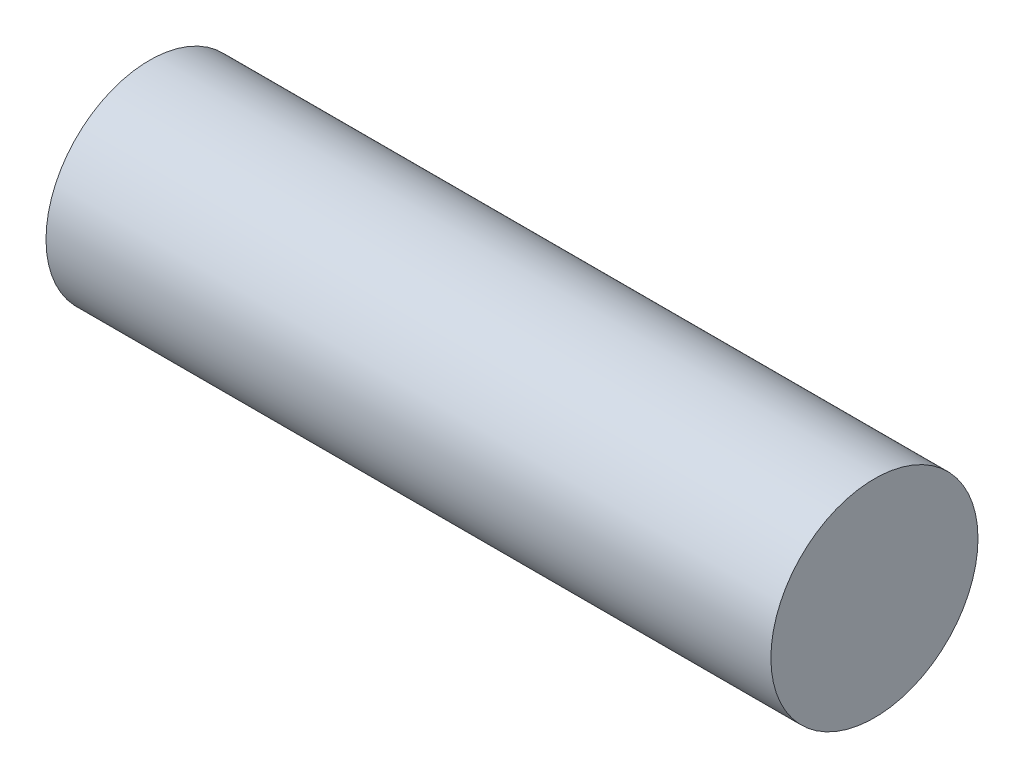
SolidWorks part; units mm, degrees
ref_plane "Front Plane" through (0, 0, 0) normal (0, 0, 1) x (1, 0, 0)
ref_plane "Top Plane" through (0, 0, 0) normal (0, 1, 0) x (1, 0, 0)
ref_plane "Right Plane" through (0, 0, 0) normal (1, 0, 0) x (0, 0, -1)
sketch "Sketch1" plane through (0, 0, 0) normal (1, 0, 0) x (0, 0, -1)
  circle A0 centre (0, 0) radius 25.4
  dimension "D1" = 50.8
extrude "Boss-Extrude1" add sketch "Sketch1" along normal blind 177.8
